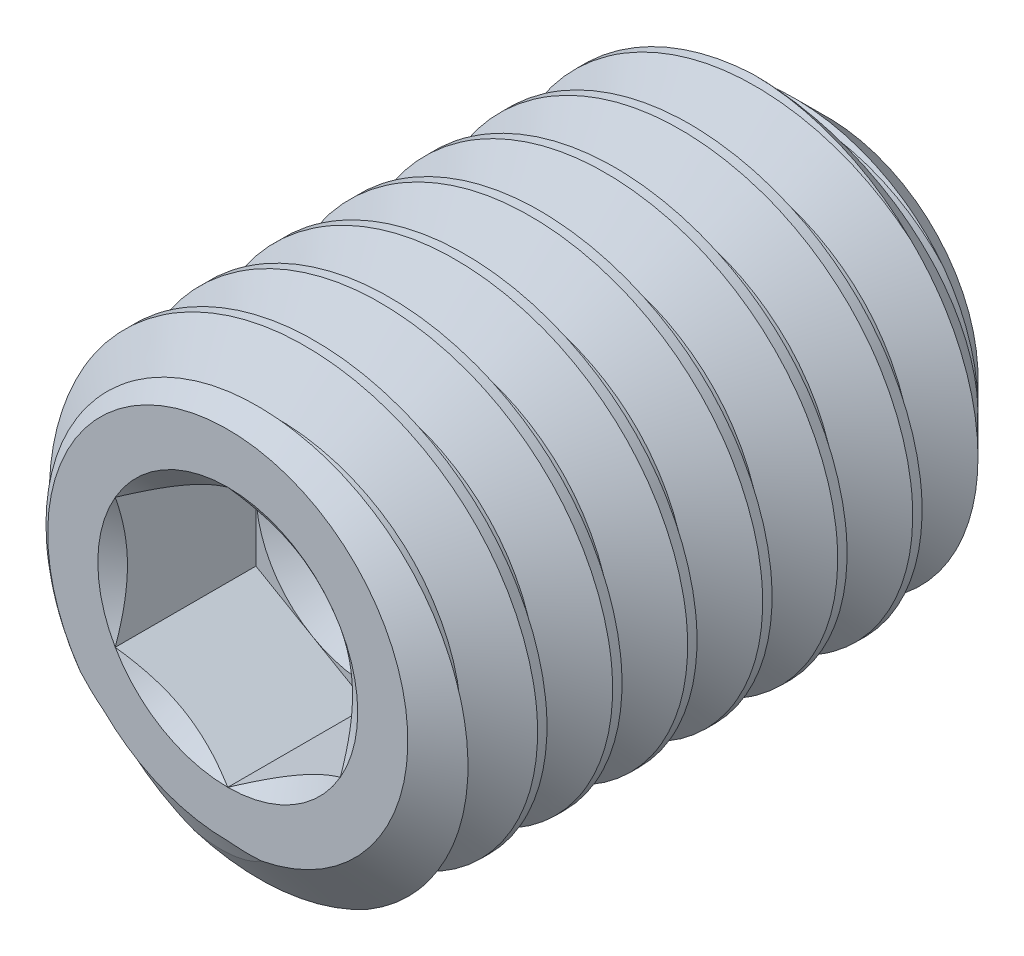
SolidWorks part; units mm, degrees
ref_plane "Front" through (0, 0, 0) normal (0, 0, 1) x (1, 0, 0)
ref_plane "Top" through (0, 0, 0) normal (0, 1, 0) x (1, 0, 0)
ref_plane "Right" through (0, 0, 0) normal (1, 0, 0) x (0, 0, -1)
sketch "Sketch22" plane through (0, 0, 0) normal (1, 0, 0) x (0, 0, -1)
  line L0 (-2, 0) -> (-2, 1.2)
  line L1 (-2, 1.2) -> (-1.7899, 1.5)
  line L2 (-1.7899, 1.5) -> (1.5, 1.5)
  line L3 (1.5, 1.5) -> (2, 1)
  line L4 (-0.145, 1.5) -> (-0.145, -1.5) construction
  line L5 (2, 0) -> (-2, 0)
  line L6 (-2, 1.2) -> (-2, -1.2) construction
  line L7 (2, 0) -> (2, 1)
  point P11 (-0.145, 0)
  dimension "Length" = 4
  dimension "D3" = 35
  dimension "D6" = 45
  dimension "Dia" = 3
  dimension "D1" = 2.4
  dimension "D2" = 0.5
revolve "Revolve1" add sketch "Sketch22" angle 360 about L5
ref_plane "Plane1" through (0, 0, -2) normal (0, 0, 1) x (1, 0, 0)
sketch "Sketch27" plane through (0, 0, -2) normal (0, 0, 1) x (1, 0, 0)
  circle A0 centre (0, 0) radius 1.5 construction
  circle A1 centre (0, 0) radius 1.5
curve "Helix/Spiral1" pitch 0.5 height 4.5 radius 1.5 centre (0, 0, -2) axis (0, 0, 1) start towards (0, 1, 0)
sketch "Sketch28" plane through (0, 0, 0) normal (1, 0, 0) x (0, 0, -1)
  line L0 (2, 1.5) -> (2.4375, 1.5)
  line L1 (2.4375, 1.5) -> (2.25, 1.1752)
  line L2 (2.25, 1.1752) -> (2.1875, 1.1752)
  line L3 (2.1875, 1.1752) -> (2, 1.5)
  line L4 (2.0937, 1.3376) -> (2.3437, 1.3376) construction
  line L6 (-1.7899, 1.5) -> (1.5, 1.5) construction
  dimension "D1" = 0.0625
  dimension "D3" = 60
  dimension "D2" = 0.25
sweep "Cut-Sweep2" cut profiles "Sketch28" path "Helix/Spiral1" align with end faces yes
sketch "Sketch23" plane through (0, 0, 2) normal (0, 0, 1) x (1, 0, 0)
  line L1 (0, 0.866) -> (-0.75, 0.433)
  line L2 (-0.75, 0.433) -> (-0.75, -0.433)
  line L3 (-0.75, -0.433) -> (0, -0.866)
  line L4 (0, -0.866) -> (0.75, -0.433)
  line L5 (0.75, -0.433) -> (0.75, 0.433)
  line L6 (0.75, 0.433) -> (0, 0.866)
  circle A0 centre (0, 0) radius 0.75 construction
  dimension "Hex" = 1.5
extrude "Cut-Extrude10" cut sketch "Sketch23" against normal blind 0.9375
sketch "Sketch24" plane through (0, 0, 2) normal (0, 0, 1) x (1, 0, 0)
  circle A0 centre (0, 0) radius 0.866
extrude "Cut-Extrude11" cut sketch "Sketch24" against normal through all draft 55
sketch "Sketch26" plane through (0, 0, 1.0625) normal (0, 0, 1) x (1, 0, 0)
  circle A0 centre (0, 0) radius 0.75 construction
  circle A1 centre (0, 0) radius 0.75
extrude "Cut-Extrude12" cut sketch "Sketch26" against normal through all draft 60
sketch "Sketch30" plane through (0, 0, 0) normal (1, 0, 0) x (0, 0, -1)
  line L0 (-1.7899, 1.5) -> (1.5, 1.5) construction
  line L1 (-2, 0) -> (-2, 1.2) construction
  line L2 (2, 0) -> (2, 1) construction
  point P0 (-2, 1.5)
  point P1 (2, 1.5)
  point P2 (2, -1.5)
  point P11 (0.75, -1.5)
  dimension "D1" = 1.25
equation "\"D1@Sketch28\" = \"D4@Helix/Spiral1\" * .125"
equation "\"D2@Sketch28\" = \"D4@Helix/Spiral1\" * .5"
equation "\"D3@Helix/Spiral1\" = \"Length@Sketch22\" + \"D4@Helix/Spiral1\""
equation "\"D1@Sketch30\" = \"D4@Helix/Spiral1\" * 2.5"
equation "\"hex Depth@Cut-Extrude10\" = \"Hex@Sketch23\" * .625"
equation "\"D1@Sketch22\" = \"Dia@Sketch22\" * .8"
equation "\"D2@Sketch22\" = \"D4@Helix/Spiral1\""
